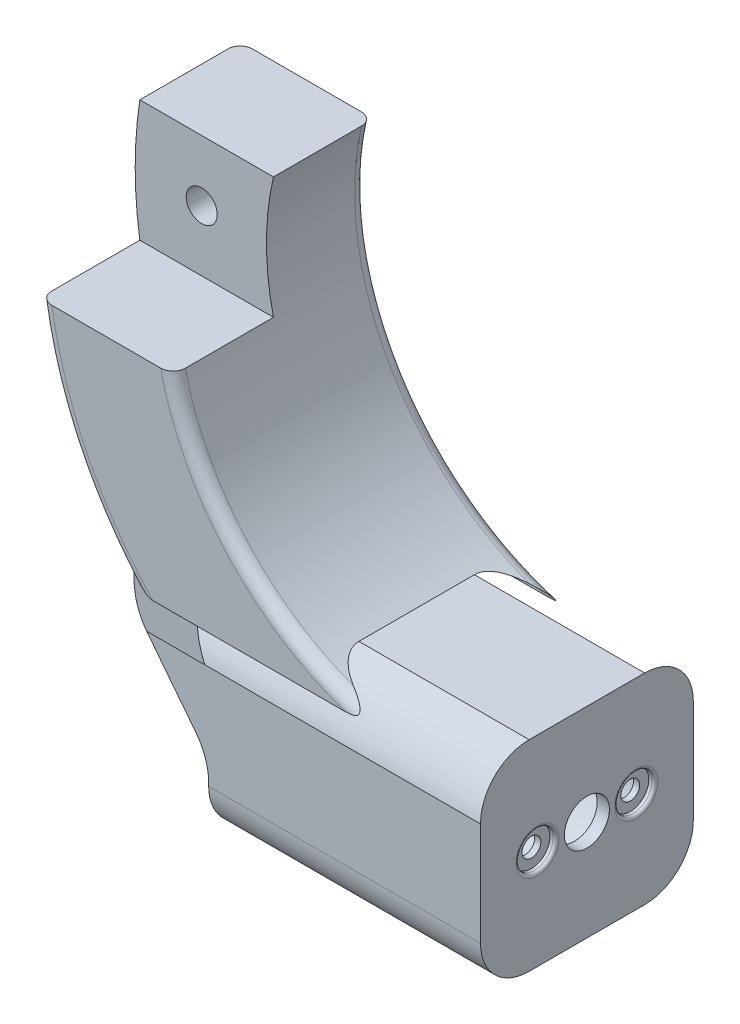
SolidWorks part; units mm, degrees
ref_plane "Front Plane" through (0, 0, 0) normal (0, 0, 1) x (1, 0, 0)
ref_plane "Top Plane" through (0, 0, 0) normal (0, 1, 0) x (1, 0, 0)
ref_plane "Right Plane" through (0, 0, 0) normal (1, 0, 0) x (0, 0, -1)
sketch "Sketch5" plane through (0, 0, -33) normal (0, 0, -1) x (-1, 0, 0)
  line L0 (31.0391, -85.25) -> (64.0391, -85.25)
  line L4 (54.5911, -55.6223) -> (76.5632, -55.6223)
  line L5 (76.5632, -35.6223) -> (54.5911, -35.6223)
  line L7 (76.5632, -35.6223) -> (54.5911, -35.6223)
  arc A0 (54.5911, -55.6223) -> (31.0391, -85.25) centre (11.6, -45.6223) cw
  arc A1 (76.5632, -55.6223) -> (64.0391, -85.25) centre (11.6, -45.6223) cw
  arc A4 (54.5911, -55.6223) -> (54.5911, -35.6223) centre (11.6, -45.6223) ccw
  arc A5 (76.5632, -55.6223) -> (76.5632, -35.6223) centre (11.6, -45.6223) ccw
  arc A6 (54.5911, -55.6223) -> (54.5911, -35.6223) centre (11.6, -45.6223) ccw
  arc A7 (76.5632, -55.6223) -> (76.5632, -35.6223) centre (11.6, -45.6223) ccw
  dimension "D1" = 0
  dimension "D2" = 33
extrude "Boss-Extrude1" add sketch "Sketch5" against normal blind 33
fillet "Fillet1" radius 2 4 edges at (-75.3303, -61.7053, -33) (-75.3303, -61.7053, 0) (-51.4762, -64.5465, 0) (-51.4762, -64.5465, -33)
sketch "Sketch6" plane through (0, 0, -16.5) normal (0, 0, -1) x (-1, 0, 0)
  line L2 (54.5911, -55.6223) -> (76.5632, -55.6223)
  line L3 (76.5632, -35.6223) -> (54.5911, -35.6223)
  line L4 (54.5911, -55.6223) -> (76.5632, -55.6223)
  line L5 (76.5632, -35.6223) -> (54.5911, -35.6223)
  arc A2 (54.5911, -55.6223) -> (54.5911, -35.6223) centre (11.6, -45.6223) ccw
  arc A3 (76.5632, -55.6223) -> (76.5632, -35.6223) centre (11.6, -45.6223) ccw
  arc A4 (54.5911, -55.6223) -> (54.5911, -35.6223) centre (11.6, -45.6223) ccw
  arc A5 (76.5632, -55.6223) -> (76.5632, -35.6223) centre (11.6, -45.6223) ccw
  dimension "D1" = 0
extrude "Cut-Extrude1" cut sketch "Sketch6" against normal through all
sketch "Sketch7" plane through (0, 0, -33) normal (0, 0, -1) x (-1, 0, 0)
  circle A0 centre (66.3894, -45.6223) radius 2.55 construction
  circle A1 centre (66.3894, -45.6223) radius 2.55
extrude "Cut-Extrude2" cut sketch "Sketch7" against normal through all
sketch "Sketch8" plane through (0, -85.25, 0) normal (0, -1, 0) x (1, 0, 0)
  line L0 (-31.0391, -16.5) -> (-64.0391, -16.5) construction
  line L2 (-5.0391, 1) -> (-80.0391, 1)
  line L3 (-5.0391, 1) -> (-5.0391, -34)
  line L4 (-64.0391, -2) -> (-64.0391, -31)
  line L5 (-61.5094, -33) -> (-35.2312, -33)
  line L6 (-31.0391, -31) -> (-31.0391, -2)
  line L7 (-35.2312, 0) -> (-61.5094, 0)
  line L8 (-64.0391, -2) -> (-64.0391, -31) construction
  line L9 (-61.5094, -33) -> (-35.2312, -33) construction
  line L10 (-31.0391, -31) -> (-31.0391, -2) construction
  line L11 (-35.2312, 0) -> (-61.5094, 0) construction
  line L12 (-5.0391, -34) -> (-80.0391, -34)
  line L13 (-80.0391, 1) -> (-80.0391, -34)
  line L14 (-5.0391, 1) -> (-80.0391, -34) construction
  line L15 (-5.0391, -34) -> (-80.0391, 1) construction
  spline S4 degree 3 poles (3861.8063, 733.6796) (237.2103, 60.9029) (-69.0926, -13.3538) (-63.9372, -31.5831) (-63.8768, -31.7218) (-63.7262, -31.9774) (-63.6343, -32.0975) (-63.4294, -32.3131) (-63.316, -32.4098) (-63.0712, -32.5821) (-62.9424, -32.6559) (-62.6737, -32.7823) (-62.5327, -32.835) (-38.7975, -39.736) (57.6195, 243.3563) (-4045.8809, -248.1128) knots -15.677405 -15.677405 -15.677405 -15.677405 0.125 0.125 0.25 0.25 0.375 0.375 0.5 0.5 0.625 0.625 0.75 0.75 21.415607 21.415607 21.415607 21.415607 only from (-64.0391, -31) to (-61.5094, -33)
  spline S5 degree 3 poles (-845.2917, 3882.356) (-204.2243, 391.8642) (-81.7875, -40.5827) (-33.5876, -32.8357) (-33.1862, -32.7392) (-32.5949, -32.5299) (-32.4012, -32.4496) (-32.0271, -32.2625) (-31.8461, -32.1554) (-31.5977, -31.9687) (-31.5185, -31.902) (-31.37, -31.756) (-31.2999, -31.6758) (-26.0157, -24.067) (-94.9331, 42.3352) (-3687.0514, -1649.0698) knots -29.123642 -29.123642 -29.123642 -29.123642 0.25 0.25 0.5 0.5 0.625 0.625 0.75 0.75 0.8125 0.8125 0.875 0.875 6.318151 6.318151 6.318151 6.318151 only from (-35.2312, -33) to (-31.0391, -31)
  spline S6 degree 3 poles (-3746.2688, 1475.8653) (-97.1676, -74.575) (-25.9769, -9.0228) (-31.2979, -1.3268) (-31.3675, -1.2467) (-31.5159, -1.1002) (-31.5955, -1.033) (-31.8461, -0.8444) (-32.0274, -0.7374) (-32.3984, -0.5516) (-32.5901, -0.472) (-32.9827, -0.3326) (-33.1837, -0.2731) (-33.5864, -0.1729) (-33.7891, -0.1319) (-84.583, 8.0412) (-208.7708, -478.706) (-773.7407, -3929.361) knots -5.392416 -5.392416 -5.392416 -5.392416 0.125 0.125 0.1875 0.1875 0.25 0.25 0.375 0.375 0.5 0.5 0.625 0.625 0.75 0.75 31.758712 31.758712 31.758712 31.758712 only from (-31.0391, -2) to (-35.2312, 0)
  spline S7 degree 3 poles (-587.6612, 3963.4932) (118.6266, -657.2905) (-26.4558, 10.2926) (-62.5307, -0.1643) (-62.6715, -0.2169) (-62.9397, -0.3427) (-63.0683, -0.4161) (-63.3126, -0.5875) (-63.4272, -0.6849) (-63.6318, -0.8995) (-63.7238, -1.0191) (-63.8758, -1.276) (-63.9354, -1.412) (-68.4766, -17.3285) (164.3416, -85.7017) (2504.2589, 3054.3214) knots -31.157923 -31.157923 -31.157923 -31.157923 0.25 0.25 0.375 0.375 0.5 0.5 0.625 0.625 0.75 0.75 0.875 0.875 14.534731 14.534731 14.534731 14.534731 only from (-61.5094, 0) to (-64.0391, -2)
  spline S8 degree 3 poles (-64.0391, -31) (-64.0391, -31.1504) (-64.0181, -31.2969) (-63.9372, -31.5831) (-63.8768, -31.7218) (-63.7262, -31.9774) (-63.6343, -32.0975) (-63.4294, -32.3131) (-63.316, -32.4098) (-63.0712, -32.5821) (-62.9424, -32.6559) (-62.6737, -32.7823) (-62.5327, -32.835) (-62.1046, -32.9595) (-61.8085, -33) (-61.5094, -33) knots 0 0 0 0 0.125 0.125 0.25 0.25 0.375 0.375 0.5 0.5 0.625 0.625 0.75 0.75 1 1 1 1 construction
  spline S9 degree 3 poles (-35.2312, -33) (-34.8134, -33) (-34.4012, -32.9665) (-33.5876, -32.8357) (-33.1862, -32.7392) (-32.5949, -32.5299) (-32.4012, -32.4496) (-32.0271, -32.2625) (-31.8461, -32.1554) (-31.5977, -31.9687) (-31.5185, -31.902) (-31.37, -31.756) (-31.2999, -31.6758) (-31.12, -31.4167) (-31.0391, -31.2129) (-31.0391, -31) knots 0 0 0 0 0.25 0.25 0.5 0.5 0.625 0.625 0.75 0.75 0.8125 0.8125 0.875 0.875 1 1 1 1 construction
  spline S10 degree 3 poles (-31.0391, -2) (-31.0391, -1.7876) (-31.1191, -1.5854) (-31.2979, -1.3268) (-31.3675, -1.2467) (-31.5159, -1.1002) (-31.5955, -1.033) (-31.8461, -0.8444) (-32.0274, -0.7374) (-32.3984, -0.5516) (-32.5901, -0.472) (-32.9827, -0.3326) (-33.1837, -0.2731) (-33.5864, -0.1729) (-33.7891, -0.1319) (-34.4009, -0.0335) (-34.8136, 0) (-35.2312, 0) knots 0 0 0 0 0.125 0.125 0.1875 0.1875 0.25 0.25 0.375 0.375 0.5 0.5 0.625 0.625 0.75 0.75 1 1 1 1 construction
  spline S11 degree 3 poles (-61.5094, 0) (-61.8087, 0) (-62.1017, -0.0399) (-62.5307, -0.1643) (-62.6715, -0.2169) (-62.9397, -0.3427) (-63.0683, -0.4161) (-63.3126, -0.5875) (-63.4272, -0.6849) (-63.6318, -0.8995) (-63.7238, -1.0191) (-63.8758, -1.276) (-63.9354, -1.412) (-64.0178, -1.7006) (-64.0391, -1.8494) (-64.0391, -2) knots 0 0 0 0 0.25 0.25 0.375 0.375 0.5 0.5 0.625 0.625 0.75 0.75 0.875 0.875 1 1 1 1 construction
  point P6 (-47.5391, -16.5)
  point P8 (-42.5391, -16.5)
  dimension "D2" = 5
  dimension "D3" = 35
  dimension "D4" = 75
  dimension "D1" = 0
extrude "Boss-Extrude2" add sketch "Sketch8" along normal blind 33
sketch "Sketch9" plane through (-5.0391, 0, 0) normal (1, 0, 0) x (0, 0, -1)
  line L0 (16.5, -85.25) -> (16.5, -118.25) construction
  line L1 (-1, -101.75) -> (34, -101.75) construction
  line L4 (34, -85.25) -> (-1, -85.25)
  line L5 (-1, -85.25) -> (-1, -118.25)
  line L6 (-1, -118.25) -> (34, -118.25)
  line L7 (34, -118.25) -> (34, -85.25)
  line L8 (34, -85.25) -> (-1, -85.25) construction
  line L9 (-1, -85.25) -> (-1, -118.25) construction
  line L10 (-1, -118.25) -> (34, -118.25) construction
  line L11 (34, -118.25) -> (34, -85.25) construction
  circle A0 centre (16.5, -101.75) radius 12.55
  dimension "D2" = 25.1
  dimension "D1" = 0
extrude "Cut-Extrude3" cut sketch "Sketch9" against normal through all
fillet "Fillet2" radius 8 4 edges at (-42.5391, -118.25, 1) (-42.5391, -85.25, 1) (-42.5391, -118.25, -34) (-42.5391, -85.25, -34)
sketch "Sketch10" plane through (-5.0391, 0, 0) normal (1, 0, 0) x (0, 0, -1)
  line L0 (16.5, -118.25) -> (16.5, -85.25) construction
  line L4 (-1, -93.25) -> (-1, -110.25)
  line L5 (7, -118.25) -> (26, -118.25)
  line L6 (34, -110.25) -> (34, -93.25)
  line L7 (26, -85.25) -> (7, -85.25)
  line L8 (-1, -93.25) -> (-1, -110.25)
  line L9 (7, -118.25) -> (26, -118.25)
  line L10 (34, -110.25) -> (34, -93.25)
  line L11 (26, -85.25) -> (7, -85.25)
  circle A2 centre (16.5, -101.75) radius 3.5 construction
  arc A4 (-1, -110.25) -> (7, -118.25) centre (7, -110.25) ccw
  arc A5 (26, -118.25) -> (34, -110.25) centre (26, -110.25) ccw
  arc A6 (34, -93.25) -> (26, -85.25) centre (26, -93.25) ccw
  arc A7 (7, -85.25) -> (-1, -93.25) centre (7, -93.25) ccw
  arc A8 (-1, -110.25) -> (7, -118.25) centre (7, -110.25) ccw
  arc A9 (26, -118.25) -> (34, -110.25) centre (26, -110.25) ccw
  arc A10 (34, -93.25) -> (26, -85.25) centre (26, -93.25) ccw
  arc A11 (7, -85.25) -> (-1, -93.25) centre (7, -93.25) ccw
  circle A12 centre (16.5, -101.75) radius 3.7
  dimension "D3" = 7
  dimension "D4" = 7.4
  dimension "D1" = 0
extrude "Boss-Extrude3" add sketch "Sketch10" along normal blind 2
sketch "Sketch13" plane through (-3.0391, 0, 0) normal (1, 0, 0) x (0, 0, -1)
  line L0 (12.8, -101.75) -> (3.95, -101.75) construction
  line L1 (20.2, -101.75) -> (29.05, -101.75) construction
  line L2 (16.5, -101.75) -> (16.5, -50101.75) construction
  circle A0 centre (16.5, -101.75) radius 3.7 construction
  circle A1 centre (16.5, -101.75) radius 12.55
  circle A2 centre (16.5, -101.75) radius 12.55 construction
  circle A3 centre (16.5, -101.75) radius 3.7 construction
  circle A4 centre (8.375, -101.75) radius 1.55
  circle A5 centre (24.625, -101.75) radius 1.55
  dimension "D2" = 3.1
  dimension "D1" = 0
extrude "Cut-Extrude5" cut sketch "Sketch13" against normal up to surface (2 mm away) up to face at (-5.0391, -101.75, -20.2)
sketch "Sketch14" plane through (-3.0391, 0, 0) normal (1, 0, 0) x (0, 0, -1)
  circle A0 centre (24.625, -101.75) radius 1.55 construction
  circle A1 centre (8.375, -101.75) radius 1.55 construction
  circle A2 centre (24.625, -101.75) radius 1.55 construction
  circle A3 centre (8.375, -101.75) radius 1.55 construction
  circle A4 centre (8.375, -101.75) radius 3.05
  circle A5 centre (24.625, -101.75) radius 3.05
  dimension "D1" = 1.5
extrude "Cut-Extrude6" cut sketch "Sketch14" against normal blind 1
fillet "Fillet3" radius 0.5 2 edges at (-3.0391, -101.75, -27.675) (-3.0391, -101.75, -11.425)
sketch "Sketch12" plane through (0, 0, -33) normal (0, 0, -1) x (-1, 0, 0)
  line L0 (80.0391, -118.25) -> (3.0391, -118.25) construction
  line L1 (80.0391, -118.25) -> (80.0391, -110.25) construction
  line L6 (80.0391, -110.25) -> (80.0391, -93.25) construction
  line L7 (80.0391, -93.25) -> (80.0391, -85.25) construction
  line L8 (64.0391, -85.25) -> (80.0391, -85.25) construction
  line L9 (80.0391, -118.25) -> (38.0391, -118.25) construction
  line L10 (80.0391, -118.25) -> (80.0391, -110.25)
  line L11 (80.0391, -110.25) -> (80.0391, -93.25)
  line L12 (80.0391, -93.25) -> (80.0391, -85.25)
  line L13 (64.0391, -85.25) -> (80.0391, -85.25)
  line L14 (47.7444, -106.25) -> (47.7444, -118.25)
  line L15 (47.7444, -118.25) -> (80.0391, -118.25)
  arc A0 (62.6655, -87.005) -> (76.5632, -35.6223) centre (11.6, -45.6223) ccw construction
  arc A1 (62.6655, -87.005) -> (76.5632, -35.6223) centre (11.6, -45.6223) ccw construction
  arc A7 (64.0391, -85.25) -> (38.0391, -118.25) centre (-766.7789, 542.5915) cw construction
  arc A8 (47.7444, -106.25) -> (64.0391, -85.25) centre (-766.7789, 542.5915) ccw
  dimension "D1" = 35
  dimension "D2" = 12
extrude "Cut-Extrude4" cut sketch "Sketch12" against normal through all both and the other way through all
fillet "Fillet6" radius 10 2 edges at (-47.7444, -106.25, -1.8923) (-47.7444, -106.25, -31.1077)
fillet "Fillet8" radius 3 1 edges at (-47.7444, -118.25, -16.5) tangent propagation no
